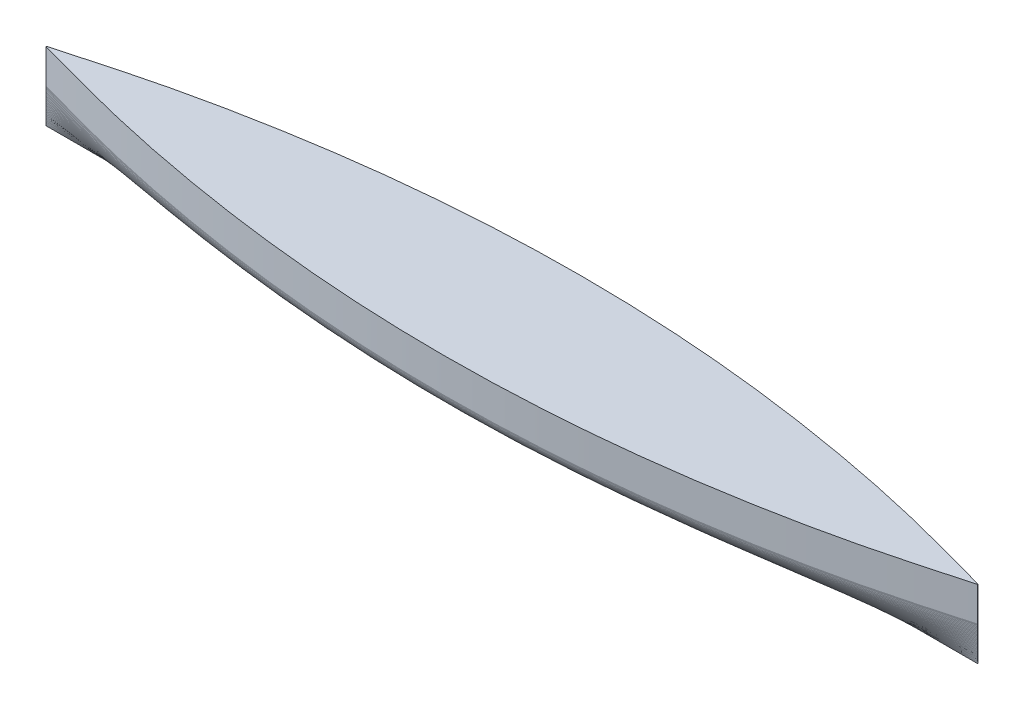
SolidWorks part; units mm, degrees
ref_plane "Plan de face" through (0, 0, 0) normal (0, 0, 1) x (1, 0, 0)
ref_plane "Plan de dessus" through (0, 0, 0) normal (0, 1, 0) x (1, 0, 0)
ref_plane "Plan de droite" through (0, 0, 0) normal (1, 0, 0) x (0, 0, -1)
ref_plane "Plan1" through (-48800, 0, 0) normal (1, 0, 0) x (0, 0, -1)
ref_plane "Plan2" through (-36600, 0, 0) normal (1, 0, 0) x (0, 0, -1)
ref_plane "Plan3" through (-24400, 0, 0) normal (1, 0, 0) x (0, 0, -1)
ref_plane "Plan4" through (-12200, 0, 0) normal (1, 0, 0) x (0, 0, -1)
ref_plane "Plan5" through (0, 0, 0) normal (1, 0, 0) x (0, 0, -1)
ref_plane "Plan6" through (12200, 0, 0) normal (1, 0, 0) x (0, 0, -1)
ref_plane "Plan7" through (24400, 0, 0) normal (1, 0, 0) x (0, 0, -1)
ref_plane "Plan8" through (36600, 0, 0) normal (1, 0, 0) x (0, 0, -1)
ref_plane "Plan9" through (48800, 0, 0) normal (1, 0, 0) x (0, 0, -1)
ref_plane "Plan10" through (-60900, 0, 0) normal (1, 0, 0) x (0, 0, -1)
ref_plane "Plan11" through (60900, 0, 0) normal (1, 0, 0) x (0, 0, -1)
sketch "Esquisse12" plane through (-60900, 0, 0) normal (1, 0, 0) x (0, 0, -1)
  line L0 (0, 0) -> (2.03, 150)
  line L1 (2.03, 150) -> (3.99, 300)
  line L2 (3.99, 300) -> (5.88, 450)
  line L3 (5.88, 450) -> (7.69, 600)
  line L4 (7.69, 600) -> (9.42, 750)
  line L5 (9.42, 750) -> (11.08, 900)
  line L6 (11.08, 900) -> (12.67, 1050)
  line L7 (12.67, 1050) -> (14.18, 1200)
  line L8 (14.18, 1200) -> (15.62, 1350)
  line L9 (15.62, 1350) -> (16.98, 1500)
  line L10 (16.98, 1500) -> (18.27, 1650)
  line L11 (18.27, 1650) -> (19.49, 1800)
  line L12 (19.49, 1800) -> (20.63, 1950)
  line L13 (20.63, 1950) -> (21.71, 2100)
  line L14 (21.71, 2100) -> (22.71, 2250)
  line L15 (22.71, 2250) -> (23.64, 2400)
  line L16 (23.64, 2400) -> (24.5, 2550)
  line L17 (24.5, 2550) -> (25.29, 2700)
  line L18 (25.29, 2700) -> (26, 2850)
  line L19 (26, 2850) -> (26.65, 3000)
  line L20 (26.65, 3000) -> (27.23, 3150)
  line L21 (27.23, 3150) -> (27.74, 3300)
  line L22 (27.74, 3300) -> (28.19, 3450)
  line L23 (28.19, 3450) -> (28.56, 3600)
  line L24 (28.56, 3600) -> (28.87, 3750)
  line L25 (28.87, 3750) -> (29.12, 3900)
  line L26 (29.12, 3900) -> (29.3, 4050)
  line L27 (29.3, 4050) -> (29.42, 4200)
  line L28 (29.42, 4200) -> (29.48, 4350)
  line L29 (29.48, 4350) -> (29.48, 4500)
  line L30 (29.48, 4500) -> (29.48, 4650)
  line L31 (29.48, 4650) -> (29.48, 4800)
  line L32 (29.48, 4800) -> (29.48, 4950)
  line L33 (29.48, 4950) -> (29.48, 5100)
  line L34 (29.48, 5100) -> (29.48, 5250)
  line L35 (29.48, 5250) -> (29.48, 5400)
  line L36 (29.48, 5400) -> (29.48, 5550)
  line L37 (29.48, 5550) -> (29.48, 5700)
  line L38 (29.48, 5700) -> (29.48, 5850)
  line L39 (29.48, 5850) -> (29.48, 6000)
  line L40 (29.48, 6000) -> (29.48, 6150)
  line L41 (29.48, 6150) -> (29.48, 6300)
  line L42 (29.48, 6300) -> (29.48, 6450)
  line L43 (29.48, 6450) -> (29.48, 6600)
  line L44 (29.48, 6600) -> (29.48, 6750)
  line L45 (29.48, 6750) -> (29.48, 6900)
  line L46 (29.48, 6900) -> (29.48, 7050)
  line L47 (29.48, 7050) -> (29.48, 7200)
  line L48 (29.48, 7200) -> (29.48, 7350)
  line L49 (29.48, 7350) -> (29.48, 7500)
  line L50 (29.48, 7500) -> (29.48, 7650)
  line L51 (29.48, 7650) -> (29.48, 7800)
  line L52 (29.48, 7800) -> (29.48, 7950)
  line L53 (29.48, 7950) -> (29.48, 8100)
  line L54 (29.48, 8100) -> (29.48, 8250)
  line L55 (29.48, 8250) -> (29.48, 8400)
  line L56 (29.48, 8400) -> (29.48, 8550)
  line L57 (29.48, 8550) -> (29.48, 8700)
  line L58 (29.48, 8700) -> (29.48, 8850)
  line L59 (29.48, 8850) -> (29.48, 9000)
  line L60 (29.48, 9000) -> (-29.48, 9000)
  line L61 (-29.48, 9000) -> (-29.48, 8850)
  line L62 (-29.48, 8850) -> (-29.48, 8700)
  line L63 (-29.48, 8700) -> (-29.48, 8550)
  line L64 (-29.48, 8550) -> (-29.48, 8400)
  line L65 (-29.48, 8400) -> (-29.48, 8250)
  line L66 (-29.48, 8250) -> (-29.48, 8100)
  line L67 (-29.48, 8100) -> (-29.48, 7950)
  line L68 (-29.48, 7950) -> (-29.48, 7800)
  line L69 (-29.48, 7800) -> (-29.48, 7650)
  line L70 (-29.48, 7650) -> (-29.48, 7500)
  line L71 (-29.48, 7500) -> (-29.48, 7350)
  line L72 (-29.48, 7350) -> (-29.48, 7200)
  line L73 (-29.48, 7200) -> (-29.48, 7050)
  line L74 (-29.48, 7050) -> (-29.48, 6900)
  line L75 (-29.48, 6900) -> (-29.48, 6750)
  line L76 (-29.48, 6750) -> (-29.48, 6600)
  line L77 (-29.48, 6600) -> (-29.48, 6450)
  line L78 (-29.48, 6450) -> (-29.48, 6300)
  line L79 (-29.48, 6300) -> (-29.48, 6150)
  line L80 (-29.48, 6150) -> (-29.48, 6000)
  line L81 (-29.48, 6000) -> (-29.48, 5850)
  line L82 (-29.48, 5850) -> (-29.48, 5700)
  line L83 (-29.48, 5700) -> (-29.48, 5550)
  line L84 (-29.48, 5550) -> (-29.48, 5400)
  line L85 (-29.48, 5400) -> (-29.48, 5250)
  line L86 (-29.48, 5250) -> (-29.48, 5100)
  line L87 (-29.48, 5100) -> (-29.48, 4950)
  line L88 (-29.48, 4950) -> (-29.48, 4800)
  line L89 (-29.48, 4800) -> (-29.48, 4650)
  line L90 (-29.48, 4650) -> (-29.48, 4500)
  line L91 (-29.48, 4500) -> (-29.48, 4350)
  line L92 (-29.48, 4350) -> (-29.42, 4200)
  line L93 (-29.42, 4200) -> (-29.3, 4050)
  line L94 (-29.3, 4050) -> (-29.12, 3900)
  line L95 (-29.12, 3900) -> (-28.87, 3750)
  line L96 (-28.87, 3750) -> (-28.56, 3600)
  line L97 (-28.56, 3600) -> (-28.19, 3450)
  line L98 (-28.19, 3450) -> (-27.74, 3300)
  line L99 (-27.74, 3300) -> (-27.23, 3150)
  line L100 (-27.23, 3150) -> (-26.65, 3000)
  line L101 (-26.65, 3000) -> (-26, 2850)
  line L102 (-26, 2850) -> (-25.29, 2700)
  line L103 (-25.29, 2700) -> (-24.5, 2550)
  line L104 (-24.5, 2550) -> (-23.64, 2400)
  line L105 (-23.64, 2400) -> (-22.71, 2250)
  line L106 (-22.71, 2250) -> (-21.71, 2100)
  line L107 (-21.71, 2100) -> (-20.63, 1950)
  line L108 (-20.63, 1950) -> (-19.49, 1800)
  line L109 (-19.49, 1800) -> (-18.27, 1650)
  line L110 (-18.27, 1650) -> (-16.98, 1500)
  line L111 (-16.98, 1500) -> (-15.62, 1350)
  line L112 (-15.62, 1350) -> (-14.18, 1200)
  line L113 (-14.18, 1200) -> (-12.67, 1050)
  line L114 (-12.67, 1050) -> (-11.08, 900)
  line L115 (-11.08, 900) -> (-9.42, 750)
  line L116 (-9.42, 750) -> (-7.69, 600)
  line L117 (-7.69, 600) -> (-5.88, 450)
  line L118 (-5.88, 450) -> (-3.99, 300)
  line L119 (-3.99, 300) -> (-2.03, 150)
  line L120 (-2.03, 150) -> (0, 0)
sketch "Esquisse15" plane through (60900, 0, 0) normal (1, 0, 0) x (0, 0, -1)
  line L0 (0, 0) -> (2.03, 150)
  line L1 (2.03, 150) -> (3.99, 300)
  line L2 (3.99, 300) -> (5.88, 450)
  line L3 (5.88, 450) -> (7.69, 600)
  line L4 (7.69, 600) -> (9.42, 750)
  line L5 (9.42, 750) -> (11.08, 900)
  line L6 (11.08, 900) -> (12.67, 1050)
  line L7 (12.67, 1050) -> (14.18, 1200)
  line L8 (14.18, 1200) -> (15.62, 1350)
  line L9 (15.62, 1350) -> (16.98, 1500)
  line L10 (16.98, 1500) -> (18.27, 1650)
  line L11 (18.27, 1650) -> (19.49, 1800)
  line L12 (19.49, 1800) -> (20.63, 1950)
  line L13 (20.63, 1950) -> (21.71, 2100)
  line L14 (21.71, 2100) -> (22.71, 2250)
  line L15 (22.71, 2250) -> (23.64, 2400)
  line L16 (23.64, 2400) -> (24.5, 2550)
  line L17 (24.5, 2550) -> (25.29, 2700)
  line L18 (25.29, 2700) -> (26, 2850)
  line L19 (26, 2850) -> (26.65, 3000)
  line L20 (26.65, 3000) -> (27.23, 3150)
  line L21 (27.23, 3150) -> (27.74, 3300)
  line L22 (27.74, 3300) -> (28.19, 3450)
  line L23 (28.19, 3450) -> (28.56, 3600)
  line L24 (28.56, 3600) -> (28.87, 3750)
  line L25 (28.87, 3750) -> (29.12, 3900)
  line L26 (29.12, 3900) -> (29.3, 4050)
  line L27 (29.3, 4050) -> (29.42, 4200)
  line L28 (29.42, 4200) -> (29.48, 4350)
  line L29 (29.48, 4350) -> (29.48, 4500)
  line L30 (29.48, 4500) -> (29.48, 4650)
  line L31 (29.48, 4650) -> (29.48, 4800)
  line L32 (29.48, 4800) -> (29.48, 4950)
  line L33 (29.48, 4950) -> (29.48, 5100)
  line L34 (29.48, 5100) -> (29.48, 5250)
  line L35 (29.48, 5250) -> (29.48, 5400)
  line L36 (29.48, 5400) -> (29.48, 5550)
  line L37 (29.48, 5550) -> (29.48, 5700)
  line L38 (29.48, 5700) -> (29.48, 5850)
  line L39 (29.48, 5850) -> (29.48, 6000)
  line L40 (29.48, 6000) -> (29.48, 6150)
  line L41 (29.48, 6150) -> (29.48, 6300)
  line L42 (29.48, 6300) -> (29.48, 6450)
  line L43 (29.48, 6450) -> (29.48, 6600)
  line L44 (29.48, 6600) -> (29.48, 6750)
  line L45 (29.48, 6750) -> (29.48, 6900)
  line L46 (29.48, 6900) -> (29.48, 7050)
  line L47 (29.48, 7050) -> (29.48, 7200)
  line L48 (29.48, 7200) -> (29.48, 7350)
  line L49 (29.48, 7350) -> (29.48, 7500)
  line L50 (29.48, 7500) -> (29.48, 7650)
  line L51 (29.48, 7650) -> (29.48, 7800)
  line L52 (29.48, 7800) -> (29.48, 7950)
  line L53 (29.48, 7950) -> (29.48, 8100)
  line L54 (29.48, 8100) -> (29.48, 8250)
  line L55 (29.48, 8250) -> (29.48, 8400)
  line L56 (29.48, 8400) -> (29.48, 8550)
  line L57 (29.48, 8550) -> (29.48, 8700)
  line L58 (29.48, 8700) -> (29.48, 8850)
  line L59 (29.48, 8850) -> (29.48, 9000)
  line L60 (29.48, 9000) -> (-29.48, 9000)
  line L61 (-29.48, 9000) -> (-29.48, 8850)
  line L62 (-29.48, 8850) -> (-29.48, 8700)
  line L63 (-29.48, 8700) -> (-29.48, 8550)
  line L64 (-29.48, 8550) -> (-29.48, 8400)
  line L65 (-29.48, 8400) -> (-29.48, 8250)
  line L66 (-29.48, 8250) -> (-29.48, 8100)
  line L67 (-29.48, 8100) -> (-29.48, 7950)
  line L68 (-29.48, 7950) -> (-29.48, 7800)
  line L69 (-29.48, 7800) -> (-29.48, 7650)
  line L70 (-29.48, 7650) -> (-29.48, 7500)
  line L71 (-29.48, 7500) -> (-29.48, 7350)
  line L72 (-29.48, 7350) -> (-29.48, 7200)
  line L73 (-29.48, 7200) -> (-29.48, 7050)
  line L74 (-29.48, 7050) -> (-29.48, 6900)
  line L75 (-29.48, 6900) -> (-29.48, 6750)
  line L76 (-29.48, 6750) -> (-29.48, 6600)
  line L77 (-29.48, 6600) -> (-29.48, 6450)
  line L78 (-29.48, 6450) -> (-29.48, 6300)
  line L79 (-29.48, 6300) -> (-29.48, 6150)
  line L80 (-29.48, 6150) -> (-29.48, 6000)
  line L81 (-29.48, 6000) -> (-29.48, 5850)
  line L82 (-29.48, 5850) -> (-29.48, 5700)
  line L83 (-29.48, 5700) -> (-29.48, 5550)
  line L84 (-29.48, 5550) -> (-29.48, 5400)
  line L85 (-29.48, 5400) -> (-29.48, 5250)
  line L86 (-29.48, 5250) -> (-29.48, 5100)
  line L87 (-29.48, 5100) -> (-29.48, 4950)
  line L88 (-29.48, 4950) -> (-29.48, 4800)
  line L89 (-29.48, 4800) -> (-29.48, 4650)
  line L90 (-29.48, 4650) -> (-29.48, 4500)
  line L91 (-29.48, 4500) -> (-29.48, 4350)
  line L92 (-29.48, 4350) -> (-29.42, 4200)
  line L93 (-29.42, 4200) -> (-29.3, 4050)
  line L94 (-29.3, 4050) -> (-29.12, 3900)
  line L95 (-29.12, 3900) -> (-28.87, 3750)
  line L96 (-28.87, 3750) -> (-28.56, 3600)
  line L97 (-28.56, 3600) -> (-28.19, 3450)
  line L98 (-28.19, 3450) -> (-27.74, 3300)
  line L99 (-27.74, 3300) -> (-27.23, 3150)
  line L100 (-27.23, 3150) -> (-26.65, 3000)
  line L101 (-26.65, 3000) -> (-26, 2850)
  line L102 (-26, 2850) -> (-25.29, 2700)
  line L103 (-25.29, 2700) -> (-24.5, 2550)
  line L104 (-24.5, 2550) -> (-23.64, 2400)
  line L105 (-23.64, 2400) -> (-22.71, 2250)
  line L106 (-22.71, 2250) -> (-21.71, 2100)
  line L107 (-21.71, 2100) -> (-20.63, 1950)
  line L108 (-20.63, 1950) -> (-19.49, 1800)
  line L109 (-19.49, 1800) -> (-18.27, 1650)
  line L110 (-18.27, 1650) -> (-16.98, 1500)
  line L111 (-16.98, 1500) -> (-15.62, 1350)
  line L112 (-15.62, 1350) -> (-14.18, 1200)
  line L113 (-14.18, 1200) -> (-12.67, 1050)
  line L114 (-12.67, 1050) -> (-11.08, 900)
  line L115 (-11.08, 900) -> (-9.42, 750)
  line L116 (-9.42, 750) -> (-7.69, 600)
  line L117 (-7.69, 600) -> (-5.88, 450)
  line L118 (-5.88, 450) -> (-3.99, 300)
  line L119 (-3.99, 300) -> (-2.03, 150)
  line L120 (-2.03, 150) -> (0, 0)
sketch "Esquisse1" plane through (-48800, 0, 0) normal (1, 0, 0) x (0, 0, -1)
  line L0 (0, 0) -> (223.61, 150)
  line L1 (223.61, 150) -> (438.92, 300)
  line L2 (438.92, 300) -> (645.97, 450)
  line L3 (645.97, 450) -> (844.77, 600)
  line L4 (844.77, 600) -> (1035.35, 750)
  line L5 (1035.35, 750) -> (1217.74, 900)
  line L6 (1217.74, 900) -> (1391.97, 1050)
  line L7 (1391.97, 1050) -> (1558.05, 1200)
  line L8 (1558.05, 1200) -> (1716.03, 1350)
  line L9 (1716.03, 1350) -> (1865.93, 1500)
  line L10 (1865.93, 1500) -> (2007.79, 1650)
  line L11 (2007.79, 1650) -> (2141.64, 1800)
  line L12 (2141.64, 1800) -> (2267.52, 1950)
  line L13 (2267.52, 1950) -> (2385.46, 2100)
  line L14 (2385.46, 2100) -> (2495.5, 2250)
  line L15 (2495.5, 2250) -> (2597.68, 2400)
  line L16 (2597.68, 2400) -> (2692.06, 2550)
  line L17 (2692.06, 2550) -> (2778.68, 2700)
  line L18 (2778.68, 2700) -> (2857.58, 2850)
  line L19 (2857.58, 2850) -> (2928.83, 3000)
  line L20 (2928.83, 3000) -> (2992.49, 3150)
  line L21 (2992.49, 3150) -> (3048.63, 3300)
  line L22 (3048.63, 3300) -> (3097.31, 3450)
  line L23 (3097.31, 3450) -> (3138.63, 3600)
  line L24 (3138.63, 3600) -> (3172.68, 3750)
  line L25 (3172.68, 3750) -> (3199.58, 3900)
  line L26 (3199.58, 3900) -> (3219.46, 4050)
  line L27 (3219.46, 4050) -> (3232.52, 4200)
  line L28 (3232.52, 4200) -> (3239.03, 4350)
  line L29 (3239.03, 4350) -> (3240, 4500)
  line L30 (3240, 4500) -> (3240, 4650)
  line L31 (3240, 4650) -> (3240, 4800)
  line L32 (3240, 4800) -> (3240, 4950)
  line L33 (3240, 4950) -> (3240, 5100)
  line L34 (3240, 5100) -> (3240, 5250)
  line L35 (3240, 5250) -> (3240, 5400)
  line L36 (3240, 5400) -> (3240, 5550)
  line L37 (3240, 5550) -> (3240, 5700)
  line L38 (3240, 5700) -> (3240, 5850)
  line L39 (3240, 5850) -> (3240, 6000)
  line L40 (3240, 6000) -> (3240, 6150)
  line L41 (3240, 6150) -> (3240, 6300)
  line L42 (3240, 6300) -> (3240, 6450)
  line L43 (3240, 6450) -> (3240, 6600)
  line L44 (3240, 6600) -> (3240, 6750)
  line L45 (3240, 6750) -> (3240, 6900)
  line L46 (3240, 6900) -> (3240, 7050)
  line L47 (3240, 7050) -> (3240, 7200)
  line L48 (3240, 7200) -> (3240, 7350)
  line L49 (3240, 7350) -> (3240, 7500)
  line L50 (3240, 7500) -> (3240, 7650)
  line L51 (3240, 7650) -> (3240, 7800)
  line L52 (3240, 7800) -> (3240, 7950)
  line L53 (3240, 7950) -> (3240, 8100)
  line L54 (3240, 8100) -> (3240, 8250)
  line L55 (3240, 8250) -> (3240, 8400)
  line L56 (3240, 8400) -> (3240, 8550)
  line L57 (3240, 8550) -> (3240, 8700)
  line L58 (3240, 8700) -> (3240, 8850)
  line L59 (3240, 8850) -> (3240, 9000)
  line L60 (3240, 9000) -> (-3240, 9000)
  line L61 (-3240, 9000) -> (-3240, 8850)
  line L62 (-3240, 8850) -> (-3240, 8700)
  line L63 (-3240, 8700) -> (-3240, 8550)
  line L64 (-3240, 8550) -> (-3240, 8400)
  line L65 (-3240, 8400) -> (-3240, 8250)
  line L66 (-3240, 8250) -> (-3240, 8100)
  line L67 (-3240, 8100) -> (-3240, 7950)
  line L68 (-3240, 7950) -> (-3240, 7800)
  line L69 (-3240, 7800) -> (-3240, 7650)
  line L70 (-3240, 7650) -> (-3240, 7500)
  line L71 (-3240, 7500) -> (-3240, 7350)
  line L72 (-3240, 7350) -> (-3240, 7200)
  line L73 (-3240, 7200) -> (-3240, 7050)
  line L74 (-3240, 7050) -> (-3240, 6900)
  line L75 (-3240, 6900) -> (-3240, 6750)
  line L76 (-3240, 6750) -> (-3240, 6600)
  line L77 (-3240, 6600) -> (-3240, 6450)
  line L78 (-3240, 6450) -> (-3240, 6300)
  line L79 (-3240, 6300) -> (-3240, 6150)
  line L80 (-3240, 6150) -> (-3240, 6000)
  line L81 (-3240, 6000) -> (-3240, 5850)
  line L82 (-3240, 5850) -> (-3240, 5700)
  line L83 (-3240, 5700) -> (-3240, 5550)
  line L84 (-3240, 5550) -> (-3240, 5400)
  line L85 (-3240, 5400) -> (-3240, 5250)
  line L86 (-3240, 5250) -> (-3240, 5100)
  line L87 (-3240, 5100) -> (-3240, 4950)
  line L88 (-3240, 4950) -> (-3240, 4800)
  line L89 (-3240, 4800) -> (-3240, 4650)
  line L90 (-3240, 4650) -> (-3240, 4500)
  line L91 (-3240, 4500) -> (-3239.03, 4350)
  line L92 (-3239.03, 4350) -> (-3232.52, 4200)
  line L93 (-3232.52, 4200) -> (-3219.46, 4050)
  line L94 (-3219.46, 4050) -> (-3199.58, 3900)
  line L95 (-3199.58, 3900) -> (-3172.68, 3750)
  line L96 (-3172.68, 3750) -> (-3138.63, 3600)
  line L97 (-3138.63, 3600) -> (-3097.31, 3450)
  line L98 (-3097.31, 3450) -> (-3048.63, 3300)
  line L99 (-3048.63, 3300) -> (-2992.49, 3150)
  line L100 (-2992.49, 3150) -> (-2928.83, 3000)
  line L101 (-2928.83, 3000) -> (-2857.58, 2850)
  line L102 (-2857.58, 2850) -> (-2778.68, 2700)
  line L103 (-2778.68, 2700) -> (-2692.06, 2550)
  line L104 (-2692.06, 2550) -> (-2597.68, 2400)
  line L105 (-2597.68, 2400) -> (-2495.5, 2250)
  line L106 (-2495.5, 2250) -> (-2385.46, 2100)
  line L107 (-2385.46, 2100) -> (-2267.52, 1950)
  line L108 (-2267.52, 1950) -> (-2141.64, 1800)
  line L109 (-2141.64, 1800) -> (-2007.79, 1650)
  line L110 (-2007.79, 1650) -> (-1865.93, 1500)
  line L111 (-1865.93, 1500) -> (-1716.03, 1350)
  line L112 (-1716.03, 1350) -> (-1558.05, 1200)
  line L113 (-1558.05, 1200) -> (-1391.97, 1050)
  line L114 (-1391.97, 1050) -> (-1217.74, 900)
  line L115 (-1217.74, 900) -> (-1035.35, 750)
  line L116 (-1035.35, 750) -> (-844.77, 600)
  line L117 (-844.77, 600) -> (-645.97, 450)
  line L118 (-645.97, 450) -> (-438.92, 300)
  line L119 (-438.92, 300) -> (-223.61, 150)
  line L120 (-223.61, 150) -> (0, 0)
sketch "Esquisse2" plane through (-36600, 0, 0) normal (1, 0, 0) x (0, 0, -1)
  line L0 (0, 0) -> (397.53, 150)
  line L1 (397.53, 150) -> (780.31, 300)
  line L2 (780.31, 300) -> (1148.39, 450)
  line L3 (1148.39, 450) -> (1501.82, 600)
  line L4 (1501.82, 600) -> (1840.63, 750)
  line L5 (1840.63, 750) -> (2164.88, 900)
  line L6 (2164.88, 900) -> (2474.61, 1050)
  line L7 (2474.61, 1050) -> (2769.87, 1200)
  line L8 (2769.87, 1200) -> (3050.72, 1350)
  line L9 (3050.72, 1350) -> (3317.22, 1500)
  line L10 (3317.22, 1500) -> (3569.41, 1650)
  line L11 (3569.41, 1650) -> (3807.36, 1800)
  line L12 (3807.36, 1800) -> (4031.14, 1950)
  line L13 (4031.14, 1950) -> (4240.81, 2100)
  line L14 (4240.81, 2100) -> (4436.44, 2250)
  line L15 (4436.44, 2250) -> (4618.1, 2400)
  line L16 (4618.1, 2400) -> (4785.89, 2550)
  line L17 (4785.89, 2550) -> (4939.87, 2700)
  line L18 (4939.87, 2700) -> (5080.15, 2850)
  line L19 (5080.15, 2850) -> (5206.82, 3000)
  line L20 (5206.82, 3000) -> (5319.99, 3150)
  line L21 (5319.99, 3150) -> (5419.78, 3300)
  line L22 (5419.78, 3300) -> (5506.33, 3450)
  line L23 (5506.33, 3450) -> (5579.79, 3600)
  line L24 (5579.79, 3600) -> (5640.32, 3750)
  line L25 (5640.32, 3750) -> (5688.14, 3900)
  line L26 (5688.14, 3900) -> (5723.49, 4050)
  line L27 (5723.49, 4050) -> (5746.7, 4200)
  line L28 (5746.7, 4200) -> (5758.27, 4350)
  line L29 (5758.27, 4350) -> (5760, 4500)
  line L30 (5760, 4500) -> (5760, 4650)
  line L31 (5760, 4650) -> (5760, 4800)
  line L32 (5760, 4800) -> (5760, 4950)
  line L33 (5760, 4950) -> (5760, 5100)
  line L34 (5760, 5100) -> (5760, 5250)
  line L35 (5760, 5250) -> (5760, 5400)
  line L36 (5760, 5400) -> (5760, 5550)
  line L37 (5760, 5550) -> (5760, 5700)
  line L38 (5760, 5700) -> (5760, 5850)
  line L39 (5760, 5850) -> (5760, 6000)
  line L40 (5760, 6000) -> (5760, 6150)
  line L41 (5760, 6150) -> (5760, 6300)
  line L42 (5760, 6300) -> (5760, 6450)
  line L43 (5760, 6450) -> (5760, 6600)
  line L44 (5760, 6600) -> (5760, 6750)
  line L45 (5760, 6750) -> (5760, 6900)
  line L46 (5760, 6900) -> (5760, 7050)
  line L47 (5760, 7050) -> (5760, 7200)
  line L48 (5760, 7200) -> (5760, 7350)
  line L49 (5760, 7350) -> (5760, 7500)
  line L50 (5760, 7500) -> (5760, 7650)
  line L51 (5760, 7650) -> (5760, 7800)
  line L52 (5760, 7800) -> (5760, 7950)
  line L53 (5760, 7950) -> (5760, 8100)
  line L54 (5760, 8100) -> (5760, 8250)
  line L55 (5760, 8250) -> (5760, 8400)
  line L56 (5760, 8400) -> (5760, 8550)
  line L57 (5760, 8550) -> (5760, 8700)
  line L58 (5760, 8700) -> (5760, 8850)
  line L59 (5760, 8850) -> (5760, 9000)
  line L60 (5760, 9000) -> (-5760, 9000)
  line L61 (-5760, 9000) -> (-5760, 8850)
  line L62 (-5760, 8850) -> (-5760, 8700)
  line L63 (-5760, 8700) -> (-5760, 8550)
  line L64 (-5760, 8550) -> (-5760, 8400)
  line L65 (-5760, 8400) -> (-5760, 8250)
  line L66 (-5760, 8250) -> (-5760, 8100)
  line L67 (-5760, 8100) -> (-5760, 7950)
  line L68 (-5760, 7950) -> (-5760, 7800)
  line L69 (-5760, 7800) -> (-5760, 7650)
  line L70 (-5760, 7650) -> (-5760, 7500)
  line L71 (-5760, 7500) -> (-5760, 7350)
  line L72 (-5760, 7350) -> (-5760, 7200)
  line L73 (-5760, 7200) -> (-5760, 7050)
  line L74 (-5760, 7050) -> (-5760, 6900)
  line L75 (-5760, 6900) -> (-5760, 6750)
  line L76 (-5760, 6750) -> (-5760, 6600)
  line L77 (-5760, 6600) -> (-5760, 6450)
  line L78 (-5760, 6450) -> (-5760, 6300)
  line L79 (-5760, 6300) -> (-5760, 6150)
  line L80 (-5760, 6150) -> (-5760, 6000)
  line L81 (-5760, 6000) -> (-5760, 5850)
  line L82 (-5760, 5850) -> (-5760, 5700)
  line L83 (-5760, 5700) -> (-5760, 5550)
  line L84 (-5760, 5550) -> (-5760, 5400)
  line L85 (-5760, 5400) -> (-5760, 5250)
  line L86 (-5760, 5250) -> (-5760, 5100)
  line L87 (-5760, 5100) -> (-5760, 4950)
  line L88 (-5760, 4950) -> (-5760, 4800)
  line L89 (-5760, 4800) -> (-5760, 4650)
  line L90 (-5760, 4650) -> (-5760, 4500)
  line L91 (-5760, 4500) -> (-5758.27, 4350)
  line L92 (-5758.27, 4350) -> (-5746.7, 4200)
  line L93 (-5746.7, 4200) -> (-5723.49, 4050)
  line L94 (-5723.49, 4050) -> (-5688.14, 3900)
  line L95 (-5688.14, 3900) -> (-5640.32, 3750)
  line L96 (-5640.32, 3750) -> (-5579.79, 3600)
  line L97 (-5579.79, 3600) -> (-5506.33, 3450)
  line L98 (-5506.33, 3450) -> (-5419.78, 3300)
  line L99 (-5419.78, 3300) -> (-5319.99, 3150)
  line L100 (-5319.99, 3150) -> (-5206.82, 3000)
  line L101 (-5206.82, 3000) -> (-5080.15, 2850)
  line L102 (-5080.15, 2850) -> (-4939.87, 2700)
  line L103 (-4939.87, 2700) -> (-4785.89, 2550)
  line L104 (-4785.89, 2550) -> (-4618.1, 2400)
  line L105 (-4618.1, 2400) -> (-4436.44, 2250)
  line L106 (-4436.44, 2250) -> (-4240.81, 2100)
  line L107 (-4240.81, 2100) -> (-4031.14, 1950)
  line L108 (-4031.14, 1950) -> (-3807.36, 1800)
  line L109 (-3807.36, 1800) -> (-3569.41, 1650)
  line L110 (-3569.41, 1650) -> (-3317.22, 1500)
  line L111 (-3317.22, 1500) -> (-3050.72, 1350)
  line L112 (-3050.72, 1350) -> (-2769.87, 1200)
  line L113 (-2769.87, 1200) -> (-2474.61, 1050)
  line L114 (-2474.61, 1050) -> (-2164.88, 900)
  line L115 (-2164.88, 900) -> (-1840.63, 750)
  line L116 (-1840.63, 750) -> (-1501.82, 600)
  line L117 (-1501.82, 600) -> (-1148.39, 450)
  line L118 (-1148.39, 450) -> (-780.31, 300)
  line L119 (-780.31, 300) -> (-397.53, 150)
  line L120 (-397.53, 150) -> (0, 0)
sketch "Esquisse3" plane through (-24400, 0, 0) normal (1, 0, 0) x (0, 0, -1)
  line L0 (0, 0) -> (521.75, 150)
  line L1 (521.75, 150) -> (1024.16, 300)
  line L2 (1024.16, 300) -> (1507.26, 450)
  line L3 (1507.26, 450) -> (1971.13, 600)
  line L4 (1971.13, 600) -> (2415.82, 750)
  line L5 (2415.82, 750) -> (2841.4, 900)
  line L6 (2841.4, 900) -> (3247.92, 1050)
  line L7 (3247.92, 1050) -> (3635.45, 1200)
  line L8 (3635.45, 1200) -> (4004.07, 1350)
  line L9 (4004.07, 1350) -> (4353.85, 1500)
  line L10 (4353.85, 1500) -> (4684.85, 1650)
  line L11 (4684.85, 1650) -> (4997.16, 1800)
  line L12 (4997.16, 1800) -> (5290.87, 1950)
  line L13 (5290.87, 1950) -> (5566.06, 2100)
  line L14 (5566.06, 2100) -> (5822.83, 2250)
  line L15 (5822.83, 2250) -> (6061.26, 2400)
  line L16 (6061.26, 2400) -> (6281.48, 2550)
  line L17 (6281.48, 2550) -> (6483.58, 2700)
  line L18 (6483.58, 2700) -> (6667.69, 2850)
  line L19 (6667.69, 2850) -> (6833.95, 3000)
  line L20 (6833.95, 3000) -> (6982.49, 3150)
  line L21 (6982.49, 3150) -> (7113.47, 3300)
  line L22 (7113.47, 3300) -> (7227.06, 3450)
  line L23 (7227.06, 3450) -> (7323.47, 3600)
  line L24 (7323.47, 3600) -> (7402.92, 3750)
  line L25 (7402.92, 3750) -> (7465.68, 3900)
  line L26 (7465.68, 3900) -> (7512.08, 4050)
  line L27 (7512.08, 4050) -> (7542.55, 4200)
  line L28 (7542.55, 4200) -> (7557.73, 4350)
  line L29 (7557.73, 4350) -> (7560, 4500)
  line L30 (7560, 4500) -> (7560, 4650)
  line L31 (7560, 4650) -> (7560, 4800)
  line L32 (7560, 4800) -> (7560, 4950)
  line L33 (7560, 4950) -> (7560, 5100)
  line L34 (7560, 5100) -> (7560, 5250)
  line L35 (7560, 5250) -> (7560, 5400)
  line L36 (7560, 5400) -> (7560, 5550)
  line L37 (7560, 5550) -> (7560, 5700)
  line L38 (7560, 5700) -> (7560, 5850)
  line L39 (7560, 5850) -> (7560, 6000)
  line L40 (7560, 6000) -> (7560, 6150)
  line L41 (7560, 6150) -> (7560, 6300)
  line L42 (7560, 6300) -> (7560, 6450)
  line L43 (7560, 6450) -> (7560, 6600)
  line L44 (7560, 6600) -> (7560, 6750)
  line L45 (7560, 6750) -> (7560, 6900)
  line L46 (7560, 6900) -> (7560, 7050)
  line L47 (7560, 7050) -> (7560, 7200)
  line L48 (7560, 7200) -> (7560, 7350)
  line L49 (7560, 7350) -> (7560, 7500)
  line L50 (7560, 7500) -> (7560, 7650)
  line L51 (7560, 7650) -> (7560, 7800)
  line L52 (7560, 7800) -> (7560, 7950)
  line L53 (7560, 7950) -> (7560, 8100)
  line L54 (7560, 8100) -> (7560, 8250)
  line L55 (7560, 8250) -> (7560, 8400)
  line L56 (7560, 8400) -> (7560, 8550)
  line L57 (7560, 8550) -> (7560, 8700)
  line L58 (7560, 8700) -> (7560, 8850)
  line L59 (7560, 8850) -> (7560, 9000)
  line L60 (7560, 9000) -> (-7560, 9000)
  line L61 (-7560, 9000) -> (-7560, 8850)
  line L62 (-7560, 8850) -> (-7560, 8700)
  line L63 (-7560, 8700) -> (-7560, 8550)
  line L64 (-7560, 8550) -> (-7560, 8400)
  line L65 (-7560, 8400) -> (-7560, 8250)
  line L66 (-7560, 8250) -> (-7560, 8100)
  line L67 (-7560, 8100) -> (-7560, 7950)
  line L68 (-7560, 7950) -> (-7560, 7800)
  line L69 (-7560, 7800) -> (-7560, 7650)
  line L70 (-7560, 7650) -> (-7560, 7500)
  line L71 (-7560, 7500) -> (-7560, 7350)
  line L72 (-7560, 7350) -> (-7560, 7200)
  line L73 (-7560, 7200) -> (-7560, 7050)
  line L74 (-7560, 7050) -> (-7560, 6900)
  line L75 (-7560, 6900) -> (-7560, 6750)
  line L76 (-7560, 6750) -> (-7560, 6600)
  line L77 (-7560, 6600) -> (-7560, 6450)
  line L78 (-7560, 6450) -> (-7560, 6300)
  line L79 (-7560, 6300) -> (-7560, 6150)
  line L80 (-7560, 6150) -> (-7560, 6000)
  line L81 (-7560, 6000) -> (-7560, 5850)
  line L82 (-7560, 5850) -> (-7560, 5700)
  line L83 (-7560, 5700) -> (-7560, 5550)
  line L84 (-7560, 5550) -> (-7560, 5400)
  line L85 (-7560, 5400) -> (-7560, 5250)
  line L86 (-7560, 5250) -> (-7560, 5100)
  line L87 (-7560, 5100) -> (-7560, 4950)
  line L88 (-7560, 4950) -> (-7560, 4800)
  line L89 (-7560, 4800) -> (-7560, 4650)
  line L90 (-7560, 4650) -> (-7560, 4500)
  line L91 (-7560, 4500) -> (-7557.73, 4350)
  line L92 (-7557.73, 4350) -> (-7542.55, 4200)
  line L93 (-7542.55, 4200) -> (-7512.08, 4050)
  line L94 (-7512.08, 4050) -> (-7465.68, 3900)
  line L95 (-7465.68, 3900) -> (-7402.92, 3750)
  line L96 (-7402.92, 3750) -> (-7323.47, 3600)
  line L97 (-7323.47, 3600) -> (-7227.06, 3450)
  line L98 (-7227.06, 3450) -> (-7113.47, 3300)
  line L99 (-7113.47, 3300) -> (-6982.49, 3150)
  line L100 (-6982.49, 3150) -> (-6833.95, 3000)
  line L101 (-6833.95, 3000) -> (-6667.69, 2850)
  line L102 (-6667.69, 2850) -> (-6483.58, 2700)
  line L103 (-6483.58, 2700) -> (-6281.48, 2550)
  line L104 (-6281.48, 2550) -> (-6061.26, 2400)
  line L105 (-6061.26, 2400) -> (-5822.83, 2250)
  line L106 (-5822.83, 2250) -> (-5566.06, 2100)
  line L107 (-5566.06, 2100) -> (-5290.87, 1950)
  line L108 (-5290.87, 1950) -> (-4997.16, 1800)
  line L109 (-4997.16, 1800) -> (-4684.85, 1650)
  line L110 (-4684.85, 1650) -> (-4353.85, 1500)
  line L111 (-4353.85, 1500) -> (-4004.07, 1350)
  line L112 (-4004.07, 1350) -> (-3635.45, 1200)
  line L113 (-3635.45, 1200) -> (-3247.92, 1050)
  line L114 (-3247.92, 1050) -> (-2841.4, 900)
  line L115 (-2841.4, 900) -> (-2415.82, 750)
  line L116 (-2415.82, 750) -> (-1971.13, 600)
  line L117 (-1971.13, 600) -> (-1507.26, 450)
  line L118 (-1507.26, 450) -> (-1024.16, 300)
  line L119 (-1024.16, 300) -> (-521.75, 150)
  line L120 (-521.75, 150) -> (0, 0)
sketch "Esquisse4" plane through (-12200, 0, 0) normal (1, 0, 0) x (0, 0, -1)
  line L0 (0, 0) -> (596.29, 150)
  line L1 (596.29, 150) -> (1170.46, 300)
  line L2 (1170.46, 300) -> (1722.59, 450)
  line L3 (1722.59, 450) -> (2252.72, 600)
  line L4 (2252.72, 600) -> (2760.94, 750)
  line L5 (2760.94, 750) -> (3247.31, 900)
  line L6 (3247.31, 900) -> (3711.91, 1050)
  line L7 (3711.91, 1050) -> (4154.81, 1200)
  line L8 (4154.81, 1200) -> (4576.08, 1350)
  line L9 (4576.08, 1350) -> (4975.82, 1500)
  line L10 (4975.82, 1500) -> (5354.11, 1650)
  line L11 (5354.11, 1650) -> (5711.04, 1800)
  line L12 (5711.04, 1800) -> (6046.71, 1950)
  line L13 (6046.71, 1950) -> (6361.21, 2100)
  line L14 (6361.21, 2100) -> (6654.66, 2250)
  line L15 (6654.66, 2250) -> (6927.16, 2400)
  line L16 (6927.16, 2400) -> (7178.83, 2550)
  line L17 (7178.83, 2550) -> (7409.8, 2700)
  line L18 (7409.8, 2700) -> (7620.22, 2850)
  line L19 (7620.22, 2850) -> (7810.23, 3000)
  line L20 (7810.23, 3000) -> (7979.98, 3150)
  line L21 (7979.98, 3150) -> (8129.67, 3300)
  line L22 (8129.67, 3300) -> (8259.5, 3450)
  line L23 (8259.5, 3450) -> (8369.68, 3600)
  line L24 (8369.68, 3600) -> (8460.48, 3750)
  line L25 (8460.48, 3750) -> (8532.2, 3900)
  line L26 (8532.2, 3900) -> (8585.23, 4050)
  line L27 (8585.23, 4050) -> (8620.06, 4200)
  line L28 (8620.06, 4200) -> (8637.41, 4350)
  line L29 (8637.41, 4350) -> (8640, 4500)
  line L30 (8640, 4500) -> (8640, 4650)
  line L31 (8640, 4650) -> (8640, 4800)
  line L32 (8640, 4800) -> (8640, 4950)
  line L33 (8640, 4950) -> (8640, 5100)
  line L34 (8640, 5100) -> (8640, 5250)
  line L35 (8640, 5250) -> (8640, 5400)
  line L36 (8640, 5400) -> (8640, 5550)
  line L37 (8640, 5550) -> (8640, 5700)
  line L38 (8640, 5700) -> (8640, 5850)
  line L39 (8640, 5850) -> (8640, 6000)
  line L40 (8640, 6000) -> (8640, 6150)
  line L41 (8640, 6150) -> (8640, 6300)
  line L42 (8640, 6300) -> (8640, 6450)
  line L43 (8640, 6450) -> (8640, 6600)
  line L44 (8640, 6600) -> (8640, 6750)
  line L45 (8640, 6750) -> (8640, 6900)
  line L46 (8640, 6900) -> (8640, 7050)
  line L47 (8640, 7050) -> (8640, 7200)
  line L48 (8640, 7200) -> (8640, 7350)
  line L49 (8640, 7350) -> (8640, 7500)
  line L50 (8640, 7500) -> (8640, 7650)
  line L51 (8640, 7650) -> (8640, 7800)
  line L52 (8640, 7800) -> (8640, 7950)
  line L53 (8640, 7950) -> (8640, 8100)
  line L54 (8640, 8100) -> (8640, 8250)
  line L55 (8640, 8250) -> (8640, 8400)
  line L56 (8640, 8400) -> (8640, 8550)
  line L57 (8640, 8550) -> (8640, 8700)
  line L58 (8640, 8700) -> (8640, 8850)
  line L59 (8640, 8850) -> (8640, 9000)
  line L60 (8640, 9000) -> (-8640, 9000)
  line L61 (-8640, 9000) -> (-8640, 8850)
  line L62 (-8640, 8850) -> (-8640, 8700)
  line L63 (-8640, 8700) -> (-8640, 8550)
  line L64 (-8640, 8550) -> (-8640, 8400)
  line L65 (-8640, 8400) -> (-8640, 8250)
  line L66 (-8640, 8250) -> (-8640, 8100)
  line L67 (-8640, 8100) -> (-8640, 7950)
  line L68 (-8640, 7950) -> (-8640, 7800)
  line L69 (-8640, 7800) -> (-8640, 7650)
  line L70 (-8640, 7650) -> (-8640, 7500)
  line L71 (-8640, 7500) -> (-8640, 7350)
  line L72 (-8640, 7350) -> (-8640, 7200)
  line L73 (-8640, 7200) -> (-8640, 7050)
  line L74 (-8640, 7050) -> (-8640, 6900)
  line L75 (-8640, 6900) -> (-8640, 6750)
  line L76 (-8640, 6750) -> (-8640, 6600)
  line L77 (-8640, 6600) -> (-8640, 6450)
  line L78 (-8640, 6450) -> (-8640, 6300)
  line L79 (-8640, 6300) -> (-8640, 6150)
  line L80 (-8640, 6150) -> (-8640, 6000)
  line L81 (-8640, 6000) -> (-8640, 5850)
  line L82 (-8640, 5850) -> (-8640, 5700)
  line L83 (-8640, 5700) -> (-8640, 5550)
  line L84 (-8640, 5550) -> (-8640, 5400)
  line L85 (-8640, 5400) -> (-8640, 5250)
  line L86 (-8640, 5250) -> (-8640, 5100)
  line L87 (-8640, 5100) -> (-8640, 4950)
  line L88 (-8640, 4950) -> (-8640, 4800)
  line L89 (-8640, 4800) -> (-8640, 4650)
  line L90 (-8640, 4650) -> (-8640, 4500)
  line L91 (-8640, 4500) -> (-8637.41, 4350)
  line L92 (-8637.41, 4350) -> (-8620.06, 4200)
  line L93 (-8620.06, 4200) -> (-8585.23, 4050)
  line L94 (-8585.23, 4050) -> (-8532.2, 3900)
  line L95 (-8532.2, 3900) -> (-8460.48, 3750)
  line L96 (-8460.48, 3750) -> (-8369.68, 3600)
  line L97 (-8369.68, 3600) -> (-8259.5, 3450)
  line L98 (-8259.5, 3450) -> (-8129.67, 3300)
  line L99 (-8129.67, 3300) -> (-7979.98, 3150)
  line L100 (-7979.98, 3150) -> (-7810.23, 3000)
  line L101 (-7810.23, 3000) -> (-7620.22, 2850)
  line L102 (-7620.22, 2850) -> (-7409.8, 2700)
  line L103 (-7409.8, 2700) -> (-7178.83, 2550)
  line L104 (-7178.83, 2550) -> (-6927.16, 2400)
  line L105 (-6927.16, 2400) -> (-6654.66, 2250)
  line L106 (-6654.66, 2250) -> (-6361.21, 2100)
  line L107 (-6361.21, 2100) -> (-6046.71, 1950)
  line L108 (-6046.71, 1950) -> (-5711.04, 1800)
  line L109 (-5711.04, 1800) -> (-5354.11, 1650)
  line L110 (-5354.11, 1650) -> (-4975.82, 1500)
  line L111 (-4975.82, 1500) -> (-4576.08, 1350)
  line L112 (-4576.08, 1350) -> (-4154.81, 1200)
  line L113 (-4154.81, 1200) -> (-3711.91, 1050)
  line L114 (-3711.91, 1050) -> (-3247.31, 900)
  line L115 (-3247.31, 900) -> (-2760.94, 750)
  line L116 (-2760.94, 750) -> (-2252.72, 600)
  line L117 (-2252.72, 600) -> (-1722.59, 450)
  line L118 (-1722.59, 450) -> (-1170.46, 300)
  line L119 (-1170.46, 300) -> (-596.29, 150)
  line L120 (-596.29, 150) -> (0, 0)
sketch "Esquisse5" plane through (0, 0, 0) normal (1, 0, 0) x (0, 0, -1)
  line L0 (0, 0) -> (621.14, 150)
  line L1 (621.14, 150) -> (1219.23, 300)
  line L2 (1219.23, 300) -> (1794.36, 450)
  line L3 (1794.36, 450) -> (2346.59, 600)
  line L4 (2346.59, 600) -> (2875.98, 750)
  line L5 (2875.98, 750) -> (3382.62, 900)
  line L6 (3382.62, 900) -> (3866.57, 1050)
  line L7 (3866.57, 1050) -> (4327.92, 1200)
  line L8 (4327.92, 1200) -> (4766.75, 1350)
  line L9 (4766.75, 1350) -> (5183.15, 1500)
  line L10 (5183.15, 1500) -> (5577.2, 1650)
  line L11 (5577.2, 1650) -> (5949.01, 1800)
  line L12 (5949.01, 1800) -> (6298.66, 1950)
  line L13 (6298.66, 1950) -> (6626.26, 2100)
  line L14 (6626.26, 2100) -> (6931.94, 2250)
  line L15 (6931.94, 2250) -> (7215.79, 2400)
  line L16 (7215.79, 2400) -> (7477.95, 2550)
  line L17 (7477.95, 2550) -> (7718.55, 2700)
  line L18 (7718.55, 2700) -> (7937.73, 2850)
  line L19 (7937.73, 2850) -> (8135.65, 3000)
  line L20 (8135.65, 3000) -> (8312.48, 3150)
  line L21 (8312.48, 3150) -> (8468.41, 3300)
  line L22 (8468.41, 3300) -> (8603.64, 3450)
  line L23 (8603.64, 3450) -> (8718.42, 3600)
  line L24 (8718.42, 3600) -> (8813, 3750)
  line L25 (8813, 3750) -> (8887.71, 3900)
  line L26 (8887.71, 3900) -> (8942.95, 4050)
  line L27 (8942.95, 4050) -> (8979.23, 4200)
  line L28 (8979.23, 4200) -> (8997.3, 4350)
  line L29 (8997.3, 4350) -> (9000, 4500)
  line L30 (9000, 4500) -> (9000, 4650)
  line L31 (9000, 4650) -> (9000, 4800)
  line L32 (9000, 4800) -> (9000, 4950)
  line L33 (9000, 4950) -> (9000, 5100)
  line L34 (9000, 5100) -> (9000, 5250)
  line L35 (9000, 5250) -> (9000, 5400)
  line L36 (9000, 5400) -> (9000, 5550)
  line L37 (9000, 5550) -> (9000, 5700)
  line L38 (9000, 5700) -> (9000, 5850)
  line L39 (9000, 5850) -> (9000, 6000)
  line L40 (9000, 6000) -> (9000, 6150)
  line L41 (9000, 6150) -> (9000, 6300)
  line L42 (9000, 6300) -> (9000, 6450)
  line L43 (9000, 6450) -> (9000, 6600)
  line L44 (9000, 6600) -> (9000, 6750)
  line L45 (9000, 6750) -> (9000, 6900)
  line L46 (9000, 6900) -> (9000, 7050)
  line L47 (9000, 7050) -> (9000, 7200)
  line L48 (9000, 7200) -> (9000, 7350)
  line L49 (9000, 7350) -> (9000, 7500)
  line L50 (9000, 7500) -> (9000, 7650)
  line L51 (9000, 7650) -> (9000, 7800)
  line L52 (9000, 7800) -> (9000, 7950)
  line L53 (9000, 7950) -> (9000, 8100)
  line L54 (9000, 8100) -> (9000, 8250)
  line L55 (9000, 8250) -> (9000, 8400)
  line L56 (9000, 8400) -> (9000, 8550)
  line L57 (9000, 8550) -> (9000, 8700)
  line L58 (9000, 8700) -> (9000, 8850)
  line L59 (9000, 8850) -> (9000, 9000)
  line L60 (9000, 9000) -> (-9000, 9000)
  line L61 (-9000, 9000) -> (-9000, 8850)
  line L62 (-9000, 8850) -> (-9000, 8700)
  line L63 (-9000, 8700) -> (-9000, 8550)
  line L64 (-9000, 8550) -> (-9000, 8400)
  line L65 (-9000, 8400) -> (-9000, 8250)
  line L66 (-9000, 8250) -> (-9000, 8100)
  line L67 (-9000, 8100) -> (-9000, 7950)
  line L68 (-9000, 7950) -> (-9000, 7800)
  line L69 (-9000, 7800) -> (-9000, 7650)
  line L70 (-9000, 7650) -> (-9000, 7500)
  line L71 (-9000, 7500) -> (-9000, 7350)
  line L72 (-9000, 7350) -> (-9000, 7200)
  line L73 (-9000, 7200) -> (-9000, 7050)
  line L74 (-9000, 7050) -> (-9000, 6900)
  line L75 (-9000, 6900) -> (-9000, 6750)
  line L76 (-9000, 6750) -> (-9000, 6600)
  line L77 (-9000, 6600) -> (-9000, 6450)
  line L78 (-9000, 6450) -> (-9000, 6300)
  line L79 (-9000, 6300) -> (-9000, 6150)
  line L80 (-9000, 6150) -> (-9000, 6000)
  line L81 (-9000, 6000) -> (-9000, 5850)
  line L82 (-9000, 5850) -> (-9000, 5700)
  line L83 (-9000, 5700) -> (-9000, 5550)
  line L84 (-9000, 5550) -> (-9000, 5400)
  line L85 (-9000, 5400) -> (-9000, 5250)
  line L86 (-9000, 5250) -> (-9000, 5100)
  line L87 (-9000, 5100) -> (-9000, 4950)
  line L88 (-9000, 4950) -> (-9000, 4800)
  line L89 (-9000, 4800) -> (-9000, 4650)
  line L90 (-9000, 4650) -> (-9000, 4500)
  line L91 (-9000, 4500) -> (-8997.3, 4350)
  line L92 (-8997.3, 4350) -> (-8979.23, 4200)
  line L93 (-8979.23, 4200) -> (-8942.95, 4050)
  line L94 (-8942.95, 4050) -> (-8887.71, 3900)
  line L95 (-8887.71, 3900) -> (-8813, 3750)
  line L96 (-8813, 3750) -> (-8718.42, 3600)
  line L97 (-8718.42, 3600) -> (-8603.64, 3450)
  line L98 (-8603.64, 3450) -> (-8468.41, 3300)
  line L99 (-8468.41, 3300) -> (-8312.48, 3150)
  line L100 (-8312.48, 3150) -> (-8135.65, 3000)
  line L101 (-8135.65, 3000) -> (-7937.73, 2850)
  line L102 (-7937.73, 2850) -> (-7718.55, 2700)
  line L103 (-7718.55, 2700) -> (-7477.95, 2550)
  line L104 (-7477.95, 2550) -> (-7215.79, 2400)
  line L105 (-7215.79, 2400) -> (-6931.94, 2250)
  line L106 (-6931.94, 2250) -> (-6626.26, 2100)
  line L107 (-6626.26, 2100) -> (-6298.66, 1950)
  line L108 (-6298.66, 1950) -> (-5949.01, 1800)
  line L109 (-5949.01, 1800) -> (-5577.2, 1650)
  line L110 (-5577.2, 1650) -> (-5183.15, 1500)
  line L111 (-5183.15, 1500) -> (-4766.75, 1350)
  line L112 (-4766.75, 1350) -> (-4327.92, 1200)
  line L113 (-4327.92, 1200) -> (-3866.57, 1050)
  line L114 (-3866.57, 1050) -> (-3382.62, 900)
  line L115 (-3382.62, 900) -> (-2875.98, 750)
  line L116 (-2875.98, 750) -> (-2346.59, 600)
  line L117 (-2346.59, 600) -> (-1794.36, 450)
  line L118 (-1794.36, 450) -> (-1219.23, 300)
  line L119 (-1219.23, 300) -> (-621.14, 150)
  line L120 (-621.14, 150) -> (0, 0)
sketch "Esquisse6" plane through (12200, 0, 0) normal (1, 0, 0) x (0, 0, -1)
  line L0 (0, 0) -> (596.29, 150)
  line L1 (596.29, 150) -> (1170.46, 300)
  line L2 (1170.46, 300) -> (1722.59, 450)
  line L3 (1722.59, 450) -> (2252.72, 600)
  line L4 (2252.72, 600) -> (2760.94, 750)
  line L5 (2760.94, 750) -> (3247.31, 900)
  line L6 (3247.31, 900) -> (3711.91, 1050)
  line L7 (3711.91, 1050) -> (4154.81, 1200)
  line L8 (4154.81, 1200) -> (4576.08, 1350)
  line L9 (4576.08, 1350) -> (4975.82, 1500)
  line L10 (4975.82, 1500) -> (5354.11, 1650)
  line L11 (5354.11, 1650) -> (5711.04, 1800)
  line L12 (5711.04, 1800) -> (6046.71, 1950)
  line L13 (6046.71, 1950) -> (6361.21, 2100)
  line L14 (6361.21, 2100) -> (6654.66, 2250)
  line L15 (6654.66, 2250) -> (6927.16, 2400)
  line L16 (6927.16, 2400) -> (7178.83, 2550)
  line L17 (7178.83, 2550) -> (7409.8, 2700)
  line L18 (7409.8, 2700) -> (7620.22, 2850)
  line L19 (7620.22, 2850) -> (7810.23, 3000)
  line L20 (7810.23, 3000) -> (7979.98, 3150)
  line L21 (7979.98, 3150) -> (8129.67, 3300)
  line L22 (8129.67, 3300) -> (8259.5, 3450)
  line L23 (8259.5, 3450) -> (8369.68, 3600)
  line L24 (8369.68, 3600) -> (8460.48, 3750)
  line L25 (8460.48, 3750) -> (8532.2, 3900)
  line L26 (8532.2, 3900) -> (8585.23, 4050)
  line L27 (8585.23, 4050) -> (8620.06, 4200)
  line L28 (8620.06, 4200) -> (8637.41, 4350)
  line L29 (8637.41, 4350) -> (8640, 4500)
  line L30 (8640, 4500) -> (8640, 4650)
  line L31 (8640, 4650) -> (8640, 4800)
  line L32 (8640, 4800) -> (8640, 4950)
  line L33 (8640, 4950) -> (8640, 5100)
  line L34 (8640, 5100) -> (8640, 5250)
  line L35 (8640, 5250) -> (8640, 5400)
  line L36 (8640, 5400) -> (8640, 5550)
  line L37 (8640, 5550) -> (8640, 5700)
  line L38 (8640, 5700) -> (8640, 5850)
  line L39 (8640, 5850) -> (8640, 6000)
  line L40 (8640, 6000) -> (8640, 6150)
  line L41 (8640, 6150) -> (8640, 6300)
  line L42 (8640, 6300) -> (8640, 6450)
  line L43 (8640, 6450) -> (8640, 6600)
  line L44 (8640, 6600) -> (8640, 6750)
  line L45 (8640, 6750) -> (8640, 6900)
  line L46 (8640, 6900) -> (8640, 7050)
  line L47 (8640, 7050) -> (8640, 7200)
  line L48 (8640, 7200) -> (8640, 7350)
  line L49 (8640, 7350) -> (8640, 7500)
  line L50 (8640, 7500) -> (8640, 7650)
  line L51 (8640, 7650) -> (8640, 7800)
  line L52 (8640, 7800) -> (8640, 7950)
  line L53 (8640, 7950) -> (8640, 8100)
  line L54 (8640, 8100) -> (8640, 8250)
  line L55 (8640, 8250) -> (8640, 8400)
  line L56 (8640, 8400) -> (8640, 8550)
  line L57 (8640, 8550) -> (8640, 8700)
  line L58 (8640, 8700) -> (8640, 8850)
  line L59 (8640, 8850) -> (8640, 9000)
  line L60 (8640, 9000) -> (-8640, 9000)
  line L61 (-8640, 9000) -> (-8640, 8850)
  line L62 (-8640, 8850) -> (-8640, 8700)
  line L63 (-8640, 8700) -> (-8640, 8550)
  line L64 (-8640, 8550) -> (-8640, 8400)
  line L65 (-8640, 8400) -> (-8640, 8250)
  line L66 (-8640, 8250) -> (-8640, 8100)
  line L67 (-8640, 8100) -> (-8640, 7950)
  line L68 (-8640, 7950) -> (-8640, 7800)
  line L69 (-8640, 7800) -> (-8640, 7650)
  line L70 (-8640, 7650) -> (-8640, 7500)
  line L71 (-8640, 7500) -> (-8640, 7350)
  line L72 (-8640, 7350) -> (-8640, 7200)
  line L73 (-8640, 7200) -> (-8640, 7050)
  line L74 (-8640, 7050) -> (-8640, 6900)
  line L75 (-8640, 6900) -> (-8640, 6750)
  line L76 (-8640, 6750) -> (-8640, 6600)
  line L77 (-8640, 6600) -> (-8640, 6450)
  line L78 (-8640, 6450) -> (-8640, 6300)
  line L79 (-8640, 6300) -> (-8640, 6150)
  line L80 (-8640, 6150) -> (-8640, 6000)
  line L81 (-8640, 6000) -> (-8640, 5850)
  line L82 (-8640, 5850) -> (-8640, 5700)
  line L83 (-8640, 5700) -> (-8640, 5550)
  line L84 (-8640, 5550) -> (-8640, 5400)
  line L85 (-8640, 5400) -> (-8640, 5250)
  line L86 (-8640, 5250) -> (-8640, 5100)
  line L87 (-8640, 5100) -> (-8640, 4950)
  line L88 (-8640, 4950) -> (-8640, 4800)
  line L89 (-8640, 4800) -> (-8640, 4650)
  line L90 (-8640, 4650) -> (-8640, 4500)
  line L91 (-8640, 4500) -> (-8637.41, 4350)
  line L92 (-8637.41, 4350) -> (-8620.06, 4200)
  line L93 (-8620.06, 4200) -> (-8585.23, 4050)
  line L94 (-8585.23, 4050) -> (-8532.2, 3900)
  line L95 (-8532.2, 3900) -> (-8460.48, 3750)
  line L96 (-8460.48, 3750) -> (-8369.68, 3600)
  line L97 (-8369.68, 3600) -> (-8259.5, 3450)
  line L98 (-8259.5, 3450) -> (-8129.67, 3300)
  line L99 (-8129.67, 3300) -> (-7979.98, 3150)
  line L100 (-7979.98, 3150) -> (-7810.23, 3000)
  line L101 (-7810.23, 3000) -> (-7620.22, 2850)
  line L102 (-7620.22, 2850) -> (-7409.8, 2700)
  line L103 (-7409.8, 2700) -> (-7178.83, 2550)
  line L104 (-7178.83, 2550) -> (-6927.16, 2400)
  line L105 (-6927.16, 2400) -> (-6654.66, 2250)
  line L106 (-6654.66, 2250) -> (-6361.21, 2100)
  line L107 (-6361.21, 2100) -> (-6046.71, 1950)
  line L108 (-6046.71, 1950) -> (-5711.04, 1800)
  line L109 (-5711.04, 1800) -> (-5354.11, 1650)
  line L110 (-5354.11, 1650) -> (-4975.82, 1500)
  line L111 (-4975.82, 1500) -> (-4576.08, 1350)
  line L112 (-4576.08, 1350) -> (-4154.81, 1200)
  line L113 (-4154.81, 1200) -> (-3711.91, 1050)
  line L114 (-3711.91, 1050) -> (-3247.31, 900)
  line L115 (-3247.31, 900) -> (-2760.94, 750)
  line L116 (-2760.94, 750) -> (-2252.72, 600)
  line L117 (-2252.72, 600) -> (-1722.59, 450)
  line L118 (-1722.59, 450) -> (-1170.46, 300)
  line L119 (-1170.46, 300) -> (-596.29, 150)
  line L120 (-596.29, 150) -> (0, 0)
sketch "Esquisse7" plane through (24400, 0, 0) normal (1, 0, 0) x (0, 0, -1)
  line L0 (0, 0) -> (521.75, 150)
  line L1 (521.75, 150) -> (1024.16, 300)
  line L2 (1024.16, 300) -> (1507.26, 450)
  line L3 (1507.26, 450) -> (1971.13, 600)
  line L4 (1971.13, 600) -> (2415.82, 750)
  line L5 (2415.82, 750) -> (2841.4, 900)
  line L6 (2841.4, 900) -> (3247.92, 1050)
  line L7 (3247.92, 1050) -> (3635.45, 1200)
  line L8 (3635.45, 1200) -> (4004.07, 1350)
  line L9 (4004.07, 1350) -> (4353.85, 1500)
  line L10 (4353.85, 1500) -> (4684.85, 1650)
  line L11 (4684.85, 1650) -> (4997.16, 1800)
  line L12 (4997.16, 1800) -> (5290.87, 1950)
  line L13 (5290.87, 1950) -> (5566.06, 2100)
  line L14 (5566.06, 2100) -> (5822.83, 2250)
  line L15 (5822.83, 2250) -> (6061.26, 2400)
  line L16 (6061.26, 2400) -> (6281.48, 2550)
  line L17 (6281.48, 2550) -> (6483.58, 2700)
  line L18 (6483.58, 2700) -> (6667.69, 2850)
  line L19 (6667.69, 2850) -> (6833.95, 3000)
  line L20 (6833.95, 3000) -> (6982.49, 3150)
  line L21 (6982.49, 3150) -> (7113.47, 3300)
  line L22 (7113.47, 3300) -> (7227.06, 3450)
  line L23 (7227.06, 3450) -> (7323.47, 3600)
  line L24 (7323.47, 3600) -> (7402.92, 3750)
  line L25 (7402.92, 3750) -> (7465.68, 3900)
  line L26 (7465.68, 3900) -> (7512.08, 4050)
  line L27 (7512.08, 4050) -> (7542.55, 4200)
  line L28 (7542.55, 4200) -> (7557.73, 4350)
  line L29 (7557.73, 4350) -> (7560, 4500)
  line L30 (7560, 4500) -> (7560, 4650)
  line L31 (7560, 4650) -> (7560, 4800)
  line L32 (7560, 4800) -> (7560, 4950)
  line L33 (7560, 4950) -> (7560, 5100)
  line L34 (7560, 5100) -> (7560, 5250)
  line L35 (7560, 5250) -> (7560, 5400)
  line L36 (7560, 5400) -> (7560, 5550)
  line L37 (7560, 5550) -> (7560, 5700)
  line L38 (7560, 5700) -> (7560, 5850)
  line L39 (7560, 5850) -> (7560, 6000)
  line L40 (7560, 6000) -> (7560, 6150)
  line L41 (7560, 6150) -> (7560, 6300)
  line L42 (7560, 6300) -> (7560, 6450)
  line L43 (7560, 6450) -> (7560, 6600)
  line L44 (7560, 6600) -> (7560, 6750)
  line L45 (7560, 6750) -> (7560, 6900)
  line L46 (7560, 6900) -> (7560, 7050)
  line L47 (7560, 7050) -> (7560, 7200)
  line L48 (7560, 7200) -> (7560, 7350)
  line L49 (7560, 7350) -> (7560, 7500)
  line L50 (7560, 7500) -> (7560, 7650)
  line L51 (7560, 7650) -> (7560, 7800)
  line L52 (7560, 7800) -> (7560, 7950)
  line L53 (7560, 7950) -> (7560, 8100)
  line L54 (7560, 8100) -> (7560, 8250)
  line L55 (7560, 8250) -> (7560, 8400)
  line L56 (7560, 8400) -> (7560, 8550)
  line L57 (7560, 8550) -> (7560, 8700)
  line L58 (7560, 8700) -> (7560, 8850)
  line L59 (7560, 8850) -> (7560, 9000)
  line L60 (7560, 9000) -> (-7560, 9000)
  line L61 (-7560, 9000) -> (-7560, 8850)
  line L62 (-7560, 8850) -> (-7560, 8700)
  line L63 (-7560, 8700) -> (-7560, 8550)
  line L64 (-7560, 8550) -> (-7560, 8400)
  line L65 (-7560, 8400) -> (-7560, 8250)
  line L66 (-7560, 8250) -> (-7560, 8100)
  line L67 (-7560, 8100) -> (-7560, 7950)
  line L68 (-7560, 7950) -> (-7560, 7800)
  line L69 (-7560, 7800) -> (-7560, 7650)
  line L70 (-7560, 7650) -> (-7560, 7500)
  line L71 (-7560, 7500) -> (-7560, 7350)
  line L72 (-7560, 7350) -> (-7560, 7200)
  line L73 (-7560, 7200) -> (-7560, 7050)
  line L74 (-7560, 7050) -> (-7560, 6900)
  line L75 (-7560, 6900) -> (-7560, 6750)
  line L76 (-7560, 6750) -> (-7560, 6600)
  line L77 (-7560, 6600) -> (-7560, 6450)
  line L78 (-7560, 6450) -> (-7560, 6300)
  line L79 (-7560, 6300) -> (-7560, 6150)
  line L80 (-7560, 6150) -> (-7560, 6000)
  line L81 (-7560, 6000) -> (-7560, 5850)
  line L82 (-7560, 5850) -> (-7560, 5700)
  line L83 (-7560, 5700) -> (-7560, 5550)
  line L84 (-7560, 5550) -> (-7560, 5400)
  line L85 (-7560, 5400) -> (-7560, 5250)
  line L86 (-7560, 5250) -> (-7560, 5100)
  line L87 (-7560, 5100) -> (-7560, 4950)
  line L88 (-7560, 4950) -> (-7560, 4800)
  line L89 (-7560, 4800) -> (-7560, 4650)
  line L90 (-7560, 4650) -> (-7560, 4500)
  line L91 (-7560, 4500) -> (-7557.73, 4350)
  line L92 (-7557.73, 4350) -> (-7542.55, 4200)
  line L93 (-7542.55, 4200) -> (-7512.08, 4050)
  line L94 (-7512.08, 4050) -> (-7465.68, 3900)
  line L95 (-7465.68, 3900) -> (-7402.92, 3750)
  line L96 (-7402.92, 3750) -> (-7323.47, 3600)
  line L97 (-7323.47, 3600) -> (-7227.06, 3450)
  line L98 (-7227.06, 3450) -> (-7113.47, 3300)
  line L99 (-7113.47, 3300) -> (-6982.49, 3150)
  line L100 (-6982.49, 3150) -> (-6833.95, 3000)
  line L101 (-6833.95, 3000) -> (-6667.69, 2850)
  line L102 (-6667.69, 2850) -> (-6483.58, 2700)
  line L103 (-6483.58, 2700) -> (-6281.48, 2550)
  line L104 (-6281.48, 2550) -> (-6061.26, 2400)
  line L105 (-6061.26, 2400) -> (-5822.83, 2250)
  line L106 (-5822.83, 2250) -> (-5566.06, 2100)
  line L107 (-5566.06, 2100) -> (-5290.87, 1950)
  line L108 (-5290.87, 1950) -> (-4997.16, 1800)
  line L109 (-4997.16, 1800) -> (-4684.85, 1650)
  line L110 (-4684.85, 1650) -> (-4353.85, 1500)
  line L111 (-4353.85, 1500) -> (-4004.07, 1350)
  line L112 (-4004.07, 1350) -> (-3635.45, 1200)
  line L113 (-3635.45, 1200) -> (-3247.92, 1050)
  line L114 (-3247.92, 1050) -> (-2841.4, 900)
  line L115 (-2841.4, 900) -> (-2415.82, 750)
  line L116 (-2415.82, 750) -> (-1971.13, 600)
  line L117 (-1971.13, 600) -> (-1507.26, 450)
  line L118 (-1507.26, 450) -> (-1024.16, 300)
  line L119 (-1024.16, 300) -> (-521.75, 150)
  line L120 (-521.75, 150) -> (0, 0)
sketch "Esquisse8" plane through (36600, 0, 0) normal (1, 0, 0) x (0, 0, -1)
  line L0 (0, 0) -> (397.53, 150)
  line L1 (397.53, 150) -> (780.31, 300)
  line L2 (780.31, 300) -> (1148.39, 450)
  line L3 (1148.39, 450) -> (1501.82, 600)
  line L4 (1501.82, 600) -> (1840.63, 750)
  line L5 (1840.63, 750) -> (2164.88, 900)
  line L6 (2164.88, 900) -> (2474.61, 1050)
  line L7 (2474.61, 1050) -> (2769.87, 1200)
  line L8 (2769.87, 1200) -> (3050.72, 1350)
  line L9 (3050.72, 1350) -> (3317.22, 1500)
  line L10 (3317.22, 1500) -> (3569.41, 1650)
  line L11 (3569.41, 1650) -> (3807.36, 1800)
  line L12 (3807.36, 1800) -> (4031.14, 1950)
  line L13 (4031.14, 1950) -> (4240.81, 2100)
  line L14 (4240.81, 2100) -> (4436.44, 2250)
  line L15 (4436.44, 2250) -> (4618.1, 2400)
  line L16 (4618.1, 2400) -> (4785.89, 2550)
  line L17 (4785.89, 2550) -> (4939.87, 2700)
  line L18 (4939.87, 2700) -> (5080.15, 2850)
  line L19 (5080.15, 2850) -> (5206.82, 3000)
  line L20 (5206.82, 3000) -> (5319.99, 3150)
  line L21 (5319.99, 3150) -> (5419.78, 3300)
  line L22 (5419.78, 3300) -> (5506.33, 3450)
  line L23 (5506.33, 3450) -> (5579.79, 3600)
  line L24 (5579.79, 3600) -> (5640.32, 3750)
  line L25 (5640.32, 3750) -> (5688.14, 3900)
  line L26 (5688.14, 3900) -> (5723.49, 4050)
  line L27 (5723.49, 4050) -> (5746.7, 4200)
  line L28 (5746.7, 4200) -> (5758.27, 4350)
  line L29 (5758.27, 4350) -> (5760, 4500)
  line L30 (5760, 4500) -> (5760, 4650)
  line L31 (5760, 4650) -> (5760, 4800)
  line L32 (5760, 4800) -> (5760, 4950)
  line L33 (5760, 4950) -> (5760, 5100)
  line L34 (5760, 5100) -> (5760, 5250)
  line L35 (5760, 5250) -> (5760, 5400)
  line L36 (5760, 5400) -> (5760, 5550)
  line L37 (5760, 5550) -> (5760, 5700)
  line L38 (5760, 5700) -> (5760, 5850)
  line L39 (5760, 5850) -> (5760, 6000)
  line L40 (5760, 6000) -> (5760, 6150)
  line L41 (5760, 6150) -> (5760, 6300)
  line L42 (5760, 6300) -> (5760, 6450)
  line L43 (5760, 6450) -> (5760, 6600)
  line L44 (5760, 6600) -> (5760, 6750)
  line L45 (5760, 6750) -> (5760, 6900)
  line L46 (5760, 6900) -> (5760, 7050)
  line L47 (5760, 7050) -> (5760, 7200)
  line L48 (5760, 7200) -> (5760, 7350)
  line L49 (5760, 7350) -> (5760, 7500)
  line L50 (5760, 7500) -> (5760, 7650)
  line L51 (5760, 7650) -> (5760, 7800)
  line L52 (5760, 7800) -> (5760, 7950)
  line L53 (5760, 7950) -> (5760, 8100)
  line L54 (5760, 8100) -> (5760, 8250)
  line L55 (5760, 8250) -> (5760, 8400)
  line L56 (5760, 8400) -> (5760, 8550)
  line L57 (5760, 8550) -> (5760, 8700)
  line L58 (5760, 8700) -> (5760, 8850)
  line L59 (5760, 8850) -> (5760, 9000)
  line L60 (5760, 9000) -> (-5760, 9000)
  line L61 (-5760, 9000) -> (-5760, 8850)
  line L62 (-5760, 8850) -> (-5760, 8700)
  line L63 (-5760, 8700) -> (-5760, 8550)
  line L64 (-5760, 8550) -> (-5760, 8400)
  line L65 (-5760, 8400) -> (-5760, 8250)
  line L66 (-5760, 8250) -> (-5760, 8100)
  line L67 (-5760, 8100) -> (-5760, 7950)
  line L68 (-5760, 7950) -> (-5760, 7800)
  line L69 (-5760, 7800) -> (-5760, 7650)
  line L70 (-5760, 7650) -> (-5760, 7500)
  line L71 (-5760, 7500) -> (-5760, 7350)
  line L72 (-5760, 7350) -> (-5760, 7200)
  line L73 (-5760, 7200) -> (-5760, 7050)
  line L74 (-5760, 7050) -> (-5760, 6900)
  line L75 (-5760, 6900) -> (-5760, 6750)
  line L76 (-5760, 6750) -> (-5760, 6600)
  line L77 (-5760, 6600) -> (-5760, 6450)
  line L78 (-5760, 6450) -> (-5760, 6300)
  line L79 (-5760, 6300) -> (-5760, 6150)
  line L80 (-5760, 6150) -> (-5760, 6000)
  line L81 (-5760, 6000) -> (-5760, 5850)
  line L82 (-5760, 5850) -> (-5760, 5700)
  line L83 (-5760, 5700) -> (-5760, 5550)
  line L84 (-5760, 5550) -> (-5760, 5400)
  line L85 (-5760, 5400) -> (-5760, 5250)
  line L86 (-5760, 5250) -> (-5760, 5100)
  line L87 (-5760, 5100) -> (-5760, 4950)
  line L88 (-5760, 4950) -> (-5760, 4800)
  line L89 (-5760, 4800) -> (-5760, 4650)
  line L90 (-5760, 4650) -> (-5760, 4500)
  line L91 (-5760, 4500) -> (-5758.27, 4350)
  line L92 (-5758.27, 4350) -> (-5746.7, 4200)
  line L93 (-5746.7, 4200) -> (-5723.49, 4050)
  line L94 (-5723.49, 4050) -> (-5688.14, 3900)
  line L95 (-5688.14, 3900) -> (-5640.32, 3750)
  line L96 (-5640.32, 3750) -> (-5579.79, 3600)
  line L97 (-5579.79, 3600) -> (-5506.33, 3450)
  line L98 (-5506.33, 3450) -> (-5419.78, 3300)
  line L99 (-5419.78, 3300) -> (-5319.99, 3150)
  line L100 (-5319.99, 3150) -> (-5206.82, 3000)
  line L101 (-5206.82, 3000) -> (-5080.15, 2850)
  line L102 (-5080.15, 2850) -> (-4939.87, 2700)
  line L103 (-4939.87, 2700) -> (-4785.89, 2550)
  line L104 (-4785.89, 2550) -> (-4618.1, 2400)
  line L105 (-4618.1, 2400) -> (-4436.44, 2250)
  line L106 (-4436.44, 2250) -> (-4240.81, 2100)
  line L107 (-4240.81, 2100) -> (-4031.14, 1950)
  line L108 (-4031.14, 1950) -> (-3807.36, 1800)
  line L109 (-3807.36, 1800) -> (-3569.41, 1650)
  line L110 (-3569.41, 1650) -> (-3317.22, 1500)
  line L111 (-3317.22, 1500) -> (-3050.72, 1350)
  line L112 (-3050.72, 1350) -> (-2769.87, 1200)
  line L113 (-2769.87, 1200) -> (-2474.61, 1050)
  line L114 (-2474.61, 1050) -> (-2164.88, 900)
  line L115 (-2164.88, 900) -> (-1840.63, 750)
  line L116 (-1840.63, 750) -> (-1501.82, 600)
  line L117 (-1501.82, 600) -> (-1148.39, 450)
  line L118 (-1148.39, 450) -> (-780.31, 300)
  line L119 (-780.31, 300) -> (-397.53, 150)
  line L120 (-397.53, 150) -> (0, 0)
sketch "Esquisse9" plane through (48800, 0, 0) normal (1, 0, 0) x (0, 0, -1)
  line L0 (0, 0) -> (223.61, 150)
  line L1 (223.61, 150) -> (438.92, 300)
  line L2 (438.92, 300) -> (645.97, 450)
  line L3 (645.97, 450) -> (844.77, 600)
  line L4 (844.77, 600) -> (1035.35, 750)
  line L5 (1035.35, 750) -> (1217.74, 900)
  line L6 (1217.74, 900) -> (1391.97, 1050)
  line L7 (1391.97, 1050) -> (1558.05, 1200)
  line L8 (1558.05, 1200) -> (1716.03, 1350)
  line L9 (1716.03, 1350) -> (1865.93, 1500)
  line L10 (1865.93, 1500) -> (2007.79, 1650)
  line L11 (2007.79, 1650) -> (2141.64, 1800)
  line L12 (2141.64, 1800) -> (2267.52, 1950)
  line L13 (2267.52, 1950) -> (2385.46, 2100)
  line L14 (2385.46, 2100) -> (2495.5, 2250)
  line L15 (2495.5, 2250) -> (2597.68, 2400)
  line L16 (2597.68, 2400) -> (2692.06, 2550)
  line L17 (2692.06, 2550) -> (2778.68, 2700)
  line L18 (2778.68, 2700) -> (2857.58, 2850)
  line L19 (2857.58, 2850) -> (2928.83, 3000)
  line L20 (2928.83, 3000) -> (2992.49, 3150)
  line L21 (2992.49, 3150) -> (3048.63, 3300)
  line L22 (3048.63, 3300) -> (3097.31, 3450)
  line L23 (3097.31, 3450) -> (3138.63, 3600)
  line L24 (3138.63, 3600) -> (3172.68, 3750)
  line L25 (3172.68, 3750) -> (3199.58, 3900)
  line L26 (3199.58, 3900) -> (3219.46, 4050)
  line L27 (3219.46, 4050) -> (3232.52, 4200)
  line L28 (3232.52, 4200) -> (3239.03, 4350)
  line L29 (3239.03, 4350) -> (3240, 4500)
  line L30 (3240, 4500) -> (3240, 4650)
  line L31 (3240, 4650) -> (3240, 4800)
  line L32 (3240, 4800) -> (3240, 4950)
  line L33 (3240, 4950) -> (3240, 5100)
  line L34 (3240, 5100) -> (3240, 5250)
  line L35 (3240, 5250) -> (3240, 5400)
  line L36 (3240, 5400) -> (3240, 5550)
  line L37 (3240, 5550) -> (3240, 5700)
  line L38 (3240, 5700) -> (3240, 5850)
  line L39 (3240, 5850) -> (3240, 6000)
  line L40 (3240, 6000) -> (3240, 6150)
  line L41 (3240, 6150) -> (3240, 6300)
  line L42 (3240, 6300) -> (3240, 6450)
  line L43 (3240, 6450) -> (3240, 6600)
  line L44 (3240, 6600) -> (3240, 6750)
  line L45 (3240, 6750) -> (3240, 6900)
  line L46 (3240, 6900) -> (3240, 7050)
  line L47 (3240, 7050) -> (3240, 7200)
  line L48 (3240, 7200) -> (3240, 7350)
  line L49 (3240, 7350) -> (3240, 7500)
  line L50 (3240, 7500) -> (3240, 7650)
  line L51 (3240, 7650) -> (3240, 7800)
  line L52 (3240, 7800) -> (3240, 7950)
  line L53 (3240, 7950) -> (3240, 8100)
  line L54 (3240, 8100) -> (3240, 8250)
  line L55 (3240, 8250) -> (3240, 8400)
  line L56 (3240, 8400) -> (3240, 8550)
  line L57 (3240, 8550) -> (3240, 8700)
  line L58 (3240, 8700) -> (3240, 8850)
  line L59 (3240, 8850) -> (3240, 9000)
  line L60 (3240, 9000) -> (-3240, 9000)
  line L61 (-3240, 9000) -> (-3240, 8850)
  line L62 (-3240, 8850) -> (-3240, 8700)
  line L63 (-3240, 8700) -> (-3240, 8550)
  line L64 (-3240, 8550) -> (-3240, 8400)
  line L65 (-3240, 8400) -> (-3240, 8250)
  line L66 (-3240, 8250) -> (-3240, 8100)
  line L67 (-3240, 8100) -> (-3240, 7950)
  line L68 (-3240, 7950) -> (-3240, 7800)
  line L69 (-3240, 7800) -> (-3240, 7650)
  line L70 (-3240, 7650) -> (-3240, 7500)
  line L71 (-3240, 7500) -> (-3240, 7350)
  line L72 (-3240, 7350) -> (-3240, 7200)
  line L73 (-3240, 7200) -> (-3240, 7050)
  line L74 (-3240, 7050) -> (-3240, 6900)
  line L75 (-3240, 6900) -> (-3240, 6750)
  line L76 (-3240, 6750) -> (-3240, 6600)
  line L77 (-3240, 6600) -> (-3240, 6450)
  line L78 (-3240, 6450) -> (-3240, 6300)
  line L79 (-3240, 6300) -> (-3240, 6150)
  line L80 (-3240, 6150) -> (-3240, 6000)
  line L81 (-3240, 6000) -> (-3240, 5850)
  line L82 (-3240, 5850) -> (-3240, 5700)
  line L83 (-3240, 5700) -> (-3240, 5550)
  line L84 (-3240, 5550) -> (-3240, 5400)
  line L85 (-3240, 5400) -> (-3240, 5250)
  line L86 (-3240, 5250) -> (-3240, 5100)
  line L87 (-3240, 5100) -> (-3240, 4950)
  line L88 (-3240, 4950) -> (-3240, 4800)
  line L89 (-3240, 4800) -> (-3240, 4650)
  line L90 (-3240, 4650) -> (-3240, 4500)
  line L91 (-3240, 4500) -> (-3239.03, 4350)
  line L92 (-3239.03, 4350) -> (-3232.52, 4200)
  line L93 (-3232.52, 4200) -> (-3219.46, 4050)
  line L94 (-3219.46, 4050) -> (-3199.58, 3900)
  line L95 (-3199.58, 3900) -> (-3172.68, 3750)
  line L96 (-3172.68, 3750) -> (-3138.63, 3600)
  line L97 (-3138.63, 3600) -> (-3097.31, 3450)
  line L98 (-3097.31, 3450) -> (-3048.63, 3300)
  line L99 (-3048.63, 3300) -> (-2992.49, 3150)
  line L100 (-2992.49, 3150) -> (-2928.83, 3000)
  line L101 (-2928.83, 3000) -> (-2857.58, 2850)
  line L102 (-2857.58, 2850) -> (-2778.68, 2700)
  line L103 (-2778.68, 2700) -> (-2692.06, 2550)
  line L104 (-2692.06, 2550) -> (-2597.68, 2400)
  line L105 (-2597.68, 2400) -> (-2495.5, 2250)
  line L106 (-2495.5, 2250) -> (-2385.46, 2100)
  line L107 (-2385.46, 2100) -> (-2267.52, 1950)
  line L108 (-2267.52, 1950) -> (-2141.64, 1800)
  line L109 (-2141.64, 1800) -> (-2007.79, 1650)
  line L110 (-2007.79, 1650) -> (-1865.93, 1500)
  line L111 (-1865.93, 1500) -> (-1716.03, 1350)
  line L112 (-1716.03, 1350) -> (-1558.05, 1200)
  line L113 (-1558.05, 1200) -> (-1391.97, 1050)
  line L114 (-1391.97, 1050) -> (-1217.74, 900)
  line L115 (-1217.74, 900) -> (-1035.35, 750)
  line L116 (-1035.35, 750) -> (-844.77, 600)
  line L117 (-844.77, 600) -> (-645.97, 450)
  line L118 (-645.97, 450) -> (-438.92, 300)
  line L119 (-438.92, 300) -> (-223.61, 150)
  line L120 (-223.61, 150) -> (0, 0)
loft "Lissage1" add profiles "Esquisse12", "Esquisse1", "Esquisse2", "Esquisse3", "Esquisse4", "Esquisse5", "Esquisse6", "Esquisse7", "Esquisse8", "Esquisse9", "Esquisse15" connector at (-60900, 9000, -29.48) connector at (-48800, 9000, -3240) connector at (-36600, 9000, -5760) connector at (-24400, 9000, -7560) connector at (-12200, 9000, -8640) connector at (0, 9000, -9000) connector at (12200, 9000, -8640) connector at (24400, 9000, -7560) connector at (36600, 9000, -5760) connector at (48800, 9000, -3240) connector at (60900, 9000, -29.48)
ref_plane "Plan12" through (0, 4440, 0) normal (0, 1, 0) x (1, 0, 0)
split "Fractionner1" trim tools "Plan12" bodies to split 101 resulting bodies 102 103
